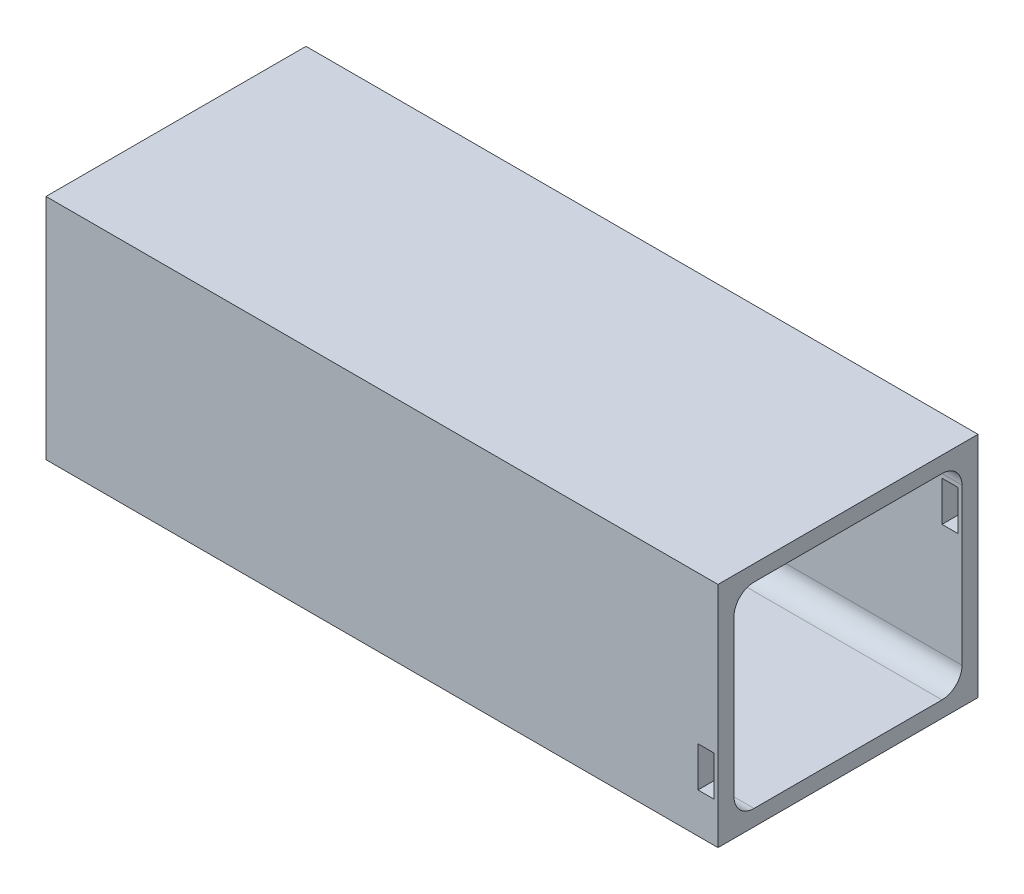
SolidWorks part; units mm, degrees
material "PET"
ref_plane "Спереди" through (0, 0, 0) normal (0, 0, 1) x (1, 0, 0)
ref_plane "Сверху" through (0, 0, 0) normal (0, 1, 0) x (1, 0, 0)
ref_plane "Справа" through (0, 0, 0) normal (1, 0, 0) x (0, 0, -1)
sketch "Эскиз1" plane through (0, 0, 0) normal (1, 0, 0) x (0, 0, -1)
  line L1 (23.5, -24.5) -> (-23.5, -24.5)
  line L2 (28.5, -19.5) -> (28.5, 19.5)
  line L3 (23.5, 24.5) -> (-23.5, 24.5)
  line L4 (-28.5, -19.5) -> (-28.5, 19.5)
  line L5 (28.5, -24.5) -> (-28.5, 24.5) construction
  line L6 (28.5, 24.5) -> (-28.5, -24.5) construction
  line L7 (32.5, -28.5) -> (-32.5, -28.5)
  line L8 (32.5, -28.5) -> (32.5, 28.5)
  line L9 (32.5, 28.5) -> (-32.5, 28.5)
  line L10 (-32.5, -28.5) -> (-32.5, 28.5)
  line L11 (32.5, -28.5) -> (-32.5, 28.5) construction
  line L12 (32.5, 28.5) -> (-32.5, -28.5) construction
  arc A0 (-23.5, -24.5) -> (-28.5, -19.5) centre (-23.5, -19.5) cw
  arc A1 (23.5, -24.5) -> (28.5, -19.5) centre (23.5, -19.5) ccw
  arc A2 (28.5, 19.5) -> (23.5, 24.5) centre (23.5, 19.5) ccw
  arc A3 (-23.5, 24.5) -> (-28.5, 19.5) centre (-23.5, 19.5) ccw
  point P0 (0, 0)
  point P5 (0, 0)
  dimension "D5" = 5
  dimension "D1" = 57
  dimension "D2" = 49
  dimension "D3" = 4
  dimension "D4" = 4
extrude "Бобышка-Вытянуть1" add sketch "Эскиз1" against normal blind 167
sketch "Эскиз2" plane through (0, 0, 32.5) normal (0, 0, 1) x (1, 0, 0)
  line L0 (0, 28.5) -> (0, -28.5) construction
  line L1 (-1, -18.5) -> (-5, -18.5)
  line L2 (-1, -18.5) -> (-1, -8.5)
  line L3 (-1, -8.5) -> (-5, -8.5)
  line L4 (-5, -18.5) -> (-5, -8.5)
  line L5 (-167, -28.5) -> (0, -28.5) construction
  dimension "D1" = 4
  dimension "D2" = 10
  dimension "D3" = 1
  dimension "D4" = 10
extrude "Вырез-Вытянуть1" cut sketch "Эскиз2" against normal blind 10
sketch "Эскиз3" plane through (-167, 0, 0) normal (-1, 0, 0) x (0, 0, 1)
  line L1 (32.5, -28.5) -> (-32.5, -28.5)
  line L2 (32.5, -28.5) -> (32.5, 28.5)
  line L3 (32.5, 28.5) -> (-32.5, 28.5)
  line L4 (-32.5, -28.5) -> (-32.5, 28.5)
  line L5 (32.5, -28.5) -> (-32.5, 28.5) construction
  line L6 (32.5, 28.5) -> (-32.5, -28.5) construction
  point P0 (0, 0)
extrude "Бобышка-Вытянуть2" add sketch "Эскиз3" along normal blind 1
sketch "Эскиз4" plane through (0, 0, -32.5) normal (0, 0, -1) x (-1, 0, 0)
  line L0 (168, 28.5) -> (0, 28.5) construction
  line L1 (1, 18.5) -> (5, 18.5)
  line L2 (1, 18.5) -> (1, 8.5)
  line L3 (1, 8.5) -> (5, 8.5)
  line L4 (5, 18.5) -> (5, 8.5)
  line L5 (0, -28.5) -> (0, 28.5) construction
  dimension "D1" = 10
  dimension "D2" = 1
  dimension "D3" = 10
  dimension "D4" = 4
extrude "Вырез-Вытянуть2" cut sketch "Эскиз4" against normal blind 10
sketch "Эскиз5" plane through (-167, 0, 0) normal (1, 0, 0) x (0, 0, -1)
  line L0 (-23.5, -24.5) -> (23.5, -24.5) construction
  line L1 (-22.5, -24.5) -> (-20.7, -24.5)
  line L2 (-22.5, -24.5) -> (-22.5, -21.5)
  line L3 (-22.5, -21.5) -> (-20.7, -21.5)
  line L4 (-20.7, -24.5) -> (-20.7, -21.5)
  line L5 (-23.5, -24.5) -> (23.5, -24.5) construction
  line L6 (-18.7, -24.5) -> (-16.9, -24.5)
  line L7 (-18.7, -24.5) -> (-18.7, -21.5)
  line L8 (-18.7, -21.5) -> (-16.9, -21.5)
  line L9 (-16.9, -24.5) -> (-16.9, -21.5)
  line L10 (-32.5, 28.5) -> (-32.5, -28.5) construction
  line L11 (-13.4, -24.5) -> (-13.4, -23)
  line L12 (-14.9, -24.5) -> (-14.4, -24.5)
  line L13 (-14.9, -24.5) -> (-14.9, -23)
  line L14 (-14.9, -23) -> (-14.4, -23)
  line L15 (-14.4, -24.5) -> (-14.4, -23)
  line L16 (-13.4, -24.5) -> (-12.9, -24.5)
  line L17 (-12.9, -24.5) -> (-12.9, -23)
  line L18 (-13.4, -23) -> (-12.9, -23)
  line L19 (-11.9, -24.5) -> (-11.9, -23)
  line L20 (-11.9, -24.5) -> (-11.4, -24.5)
  line L21 (-11.4, -24.5) -> (-11.4, -23)
  line L22 (-11.9, -23) -> (-11.4, -23)
  line L23 (-10.4, -24.5) -> (-10.4, -23)
  line L24 (-10.4, -24.5) -> (-9.9, -24.5)
  line L25 (-9.9, -24.5) -> (-9.9, -23)
  line L26 (-10.4, -23) -> (-9.9, -23)
  line L27 (-8.9, -24.5) -> (-8.9, -23)
  line L28 (-8.9, -24.5) -> (-8.4, -24.5)
  line L29 (-8.4, -24.5) -> (-8.4, -23)
  line L30 (-8.9, -23) -> (-8.4, -23)
  line L31 (-7.4, -24.5) -> (-7.4, -23)
  line L32 (-7.4, -24.5) -> (-6.9, -24.5)
  line L33 (-6.9, -24.5) -> (-6.9, -23)
  line L34 (-7.4, -23) -> (-6.9, -23)
  line L35 (-5.9, -24.5) -> (-5.9, -23)
  line L36 (-5.9, -24.5) -> (-5.4, -24.5)
  line L37 (-5.4, -24.5) -> (-5.4, -23)
  line L38 (-5.9, -23) -> (-5.4, -23)
  dimension "D1" = 10
  dimension "D2" = 1.8
  dimension "D3" = 3
  dimension "D4" = 2
  dimension "D5" = 0.5
  dimension "D6" = 1.5
  dimension "D7" = 2
  dimension "D9" = 1
  dimension "D8" = 7
extrude "Бобышка-Вытянуть3" add sketch "Эскиз5" along normal blind 2
